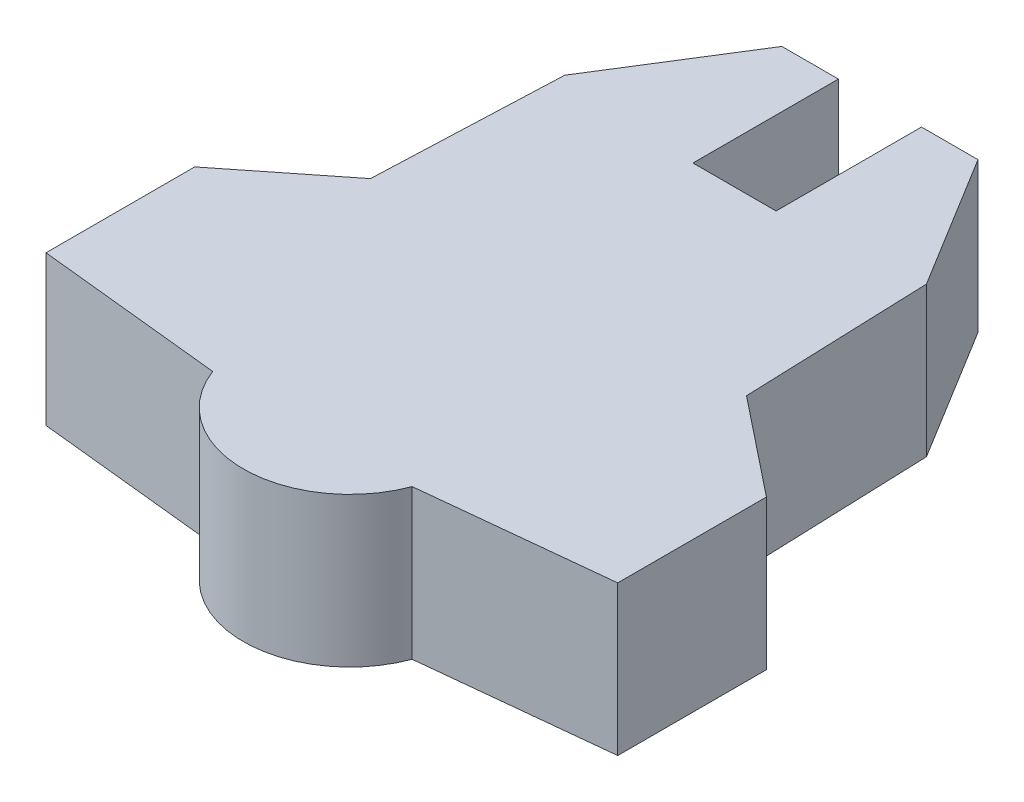
SolidWorks part; units mm, degrees
ref_plane "Front Plane" through (0, 0, 0) normal (0, 0, 1) x (1, 0, 0)
ref_plane "Top Plane" through (0, 0, 0) normal (0, 1, 0) x (1, 0, 0)
ref_plane "Right Plane" through (0, 0, 0) normal (1, 0, 0) x (0, 0, -1)
sketch "Sketch2" plane through (0, 0, 0) normal (0, 1, 0) x (1, 0, 0)
  line L0 (155.2798, 505.8339) -> (738.6131, 505.8339) construction
  line L3 (21.4236, 59.7566) -> (21.4236, 67.2801)
  line L4 (21.4236, 67.2801) -> (27.3205, 71.9569)
  line L5 (27.3205, 71.9569) -> (27.778, 83.1914)
  line L6 (27.778, 83.1914) -> (32.8106, 91.2233)
  line L7 (32.8106, 91.2233) -> (36.2106, 91.2233)
  line L8 (36.2106, 91.2233) -> (36.2106, 82.4733)
  line L9 (36.2106, 82.4733) -> (41.2106, 82.4733)
  line L10 (41.2106, 82.4733) -> (41.2106, 91.2233)
  line L11 (41.2106, 91.2233) -> (44.6106, 91.2233)
  line L12 (44.6106, 91.2233) -> (49.5416, 83.1914)
  line L13 (49.5416, 83.1914) -> (49.9483, 71.9569)
  line L14 (49.9483, 71.9569) -> (55.8236, 67.2801)
  line L15 (55.8236, 67.2801) -> (55.8236, 58.3332)
  line L16 (55.8236, 58.3332) -> (44.6236, 57.164)
  line L17 (21.4236, 59.7566) -> (21.4236, 58.3332)
  line L18 (21.4236, 58.3332) -> (32.6236, 57.164)
  arc A0 (32.6236, 57.164) -> (44.6236, 57.164) centre (38.6236, 59.4111) ccw
  dimension "D15" = 6.407
  dimension "D1" = 11.2345
  dimension "D2" = 21.4236
  dimension "D3" = 27.3205
  dimension "D4" = 8.9469
  dimension "D5" = 11.2
  dimension "D6" = 27.778
  dimension "D7" = 32.8106
  dimension "D8" = 3.4
  dimension "D9" = 5
  dimension "D10" = 12
  dimension "D11" = 57.164
  dimension "D12" = 4.6768
  dimension "D13" = 8.75
  dimension "D14" = 58.3332
  dimension "D16" = 59.7566
  dimension "D17" = 49.5416
  dimension "D18" = 49.9483
  dimension "D20" = 82.4733
extrude "Boss-Extrude1" add sketch "Sketch2" along normal blind 9
sketch "Sketch3" plane through (0, 0, 0) normal (0, -1, 0) x (1, 0, 0)
  line L0 (21.4236, -67.2801) -> (21.4236, -58.3332) construction
  circle A1 centre (38.6701, -68.7406) radius 2.5
  dimension "D1" = 5
  dimension "D2" = 17.2465
  dimension "D3" = 8.9469
  dimension "D4" = 1.4605
extrude "Boss-Extrude2" add sketch "Sketch3" along normal blind 6
